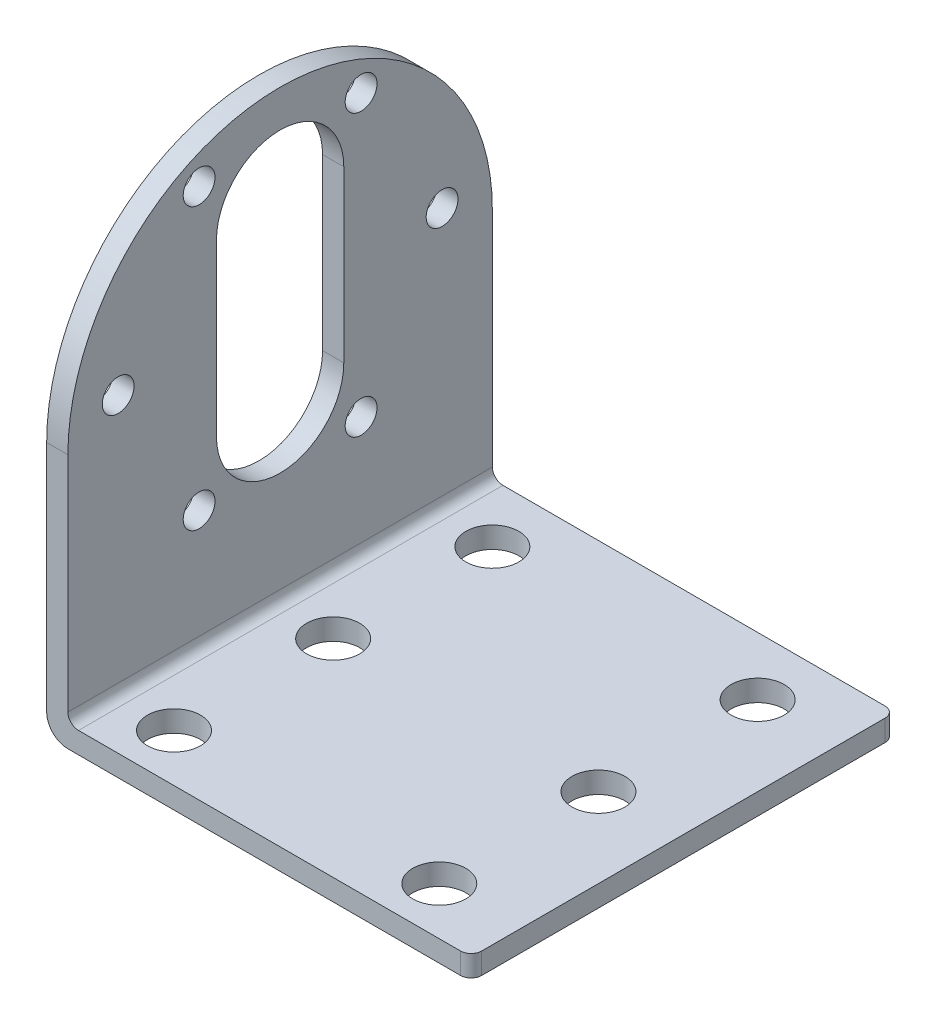
SolidWorks part; units mm, degrees
material "Ductile Iron"
ref_plane "Front Plane" through (0, 0, 0) normal (0, 0, 1) x (1, 0, 0)
ref_plane "Top Plane" through (0, 0, 0) normal (0, 1, 0) x (1, 0, 0)
ref_plane "Right Plane" through (0, 0, 0) normal (1, 0, 0) x (0, 0, -1)
sketch "Sketch2" plane through (0, 0, 0) normal (0, 0, 1) x (1, 0, 0)
  line L0 (2, 0) -> (40, 0)
  line L1 (0, 2) -> (0, 45)
  line L2 (2, 3) -> (2, 45)
  line L3 (3, 2) -> (40, 2)
  line L4 (40, 2) -> (40, 0)
  line L5 (0, 45) -> (2, 45)
  line L6 (2, 2) -> (40, 2) construction
  line L7 (2, 2) -> (2, 45) construction
  line L8 (0, 0) -> (40, 0) construction
  line L9 (0, 0) -> (0, 45) construction
  arc A0 (3, 2) -> (2, 3) centre (3, 3) cw
  arc A1 (2, 0) -> (0, 2) centre (2, 2) cw
  point P13 (0, 0)
  dimension "D4" = 1
  dimension "D5" = 2
  dimension "D1" = 40
  dimension "D3" = 45
  dimension "D2" = 2
extrude "Boss-Extrude1" add sketch "Sketch2" along normal blind 40
sketch "Sketch3" plane through (0, 2, 0) normal (0, 1, 0) x (1, 0, 0)
  line L0 (40, -40) -> (3, -40) construction
  point P0 (32.5, -35.5)
  point P6 (32.5, -5.5)
  point P9 (7.5, -5.5)
  point P11 (7.5, -35.5)
  dimension "D1" = 4.5
  dimension "D2" = 7.5
  dimension "D3" = 30
  dimension "D4" = 25
hole_wizard "Hole1" positions "Sketch3" profile "Sketch4" legacy end condition through all
sketch "Sketch4" plane through (32.5, 2, 35.5) normal (1, 0, 0) x (0, 0, 1)
  line L0 (0, 0) -> (0, 2)
  line L1 (0, 2) -> (2.5, 2)
  line L2 (2.5, 2) -> (2.5, 0)
  line L3 (2.5, 0) -> (0, 0)
  line L4 (0, 110) -> (0, -10) construction
  dimension "Diameter" = 5
  dimension "Depth" = 2
sketch "Sketch5" plane through (2, 0, 0) normal (1, 0, 0) x (0, 0, -1)
  line L0 (-40, 3) -> (-40, 45) construction
  line L1 (-40, 3) -> (-40, 45)
  line L2 (0, 3) -> (0, 45) construction
  line L3 (0, 3) -> (0, 45)
  line L4 (-40, 24) -> (-40, 3)
  line L5 (0, 3) -> (0, 24)
  arc A0 (-40, 24) -> (0, 24) centre (-20, 24) cw
  line M2 (0, 45) -> (-40, 45)
  line M3 (-40, 45) -> (-40, 3)
  dimension "D1" = 20
extrude "Cut-Extrude1" cut sketch "Sketch5" against normal blind 40 contours A0 L3 M3 M2 region at (2, 34.5, 39.5482)
sketch "Sketch6" plane through (2, 0, 0) normal (1, 0, 0) x (0, 0, -1)
  line L0 (-20, 34.5) -> (-20, 18.5) construction
  line L1 (-14, 34.5) -> (-14, 18.5)
  line L2 (-26, 34.5) -> (-26, 18.5)
  arc A0 (-14, 34.5) -> (-26, 34.5) centre (-20, 34.5) ccw
  arc A1 (-26, 18.5) -> (-14, 18.5) centre (-20, 18.5) ccw
  arc A2 (0, 24) -> (-40, 24) centre (-20, 24) ccw construction
  circle A3 centre (-20, 26.5) radius 15 construction
  point P3 (-20, 26.5)
  point P8 (-20, 40.5)
  point P9 (-20, 12.5)
  point P13 (-20, 44)
  dimension "D3" = 6
  dimension "D4" = 30
  dimension "D1" = 28
  dimension "D2" = 9.5
extrude "Cut-Extrude2" cut sketch "Sketch6" against normal blind 40
sketch "Sketch7" plane through (2, 0, 0) normal (1, 0, 0) x (0, 0, -1)
  line L0 (-20, 40.5) -> (-20, 12.5) construction
  line L1 (-35.265, 26.5) -> (-20, 26.5) construction
  line L2 (-20, 26.5) -> (-27.6325, 13.2801) construction
  arc A0 (-14, 34.5) -> (-26, 34.5) centre (-20, 34.5) ccw construction
  arc A1 (-26, 18.5) -> (-14, 18.5) centre (-20, 18.5) ccw construction
  circle A2 centre (-20, 26.5) radius 15.265 construction
  circle A3 centre (-4.735, 26.5) radius 1.5
  circle A4 centre (-35.265, 26.5) radius 1.5
  circle A5 centre (-27.6325, 13.2801) radius 1.5
  circle A6 centre (-12.3675, 13.2801) radius 1.5
  circle A7 centre (-27.6325, 39.7199) radius 1.5
  circle A8 centre (-12.3675, 39.7199) radius 1.5
  dimension "D1" = 30.53
  dimension "D2" = 3
  dimension "D3" = 3
  dimension "D4" = 3
  dimension "D6" = 3
  dimension "D7" = 3
  dimension "D8" = 3
  dimension "D5" = 60
extrude "Cut-Extrude3" cut sketch "Sketch7" against normal blind 40
fillet "Fillet1" radius 1 2 edges at (40, 1, 0) (40, 1, 40)
sketch "Sketch10" plane through (0, 2, 0) normal (0, 1, 0) x (1, 0, 0)
  line L0 (7.5, -3) -> (7.5, -38) construction
  line L1 (32.5, -3) -> (32.5, -38) construction
  circle A0 centre (7.5, -5.5) radius 2.5 construction
  circle A1 centre (7.5, -35.5) radius 2.5 construction
  circle A2 centre (32.5, -5.5) radius 2.5 construction
  circle A3 centre (32.5, -35.5) radius 2.5 construction
  circle A4 centre (7.5, -20.5) radius 2.5
  circle A5 centre (32.5, -20.5) radius 2.5
  dimension "D1" = 5
  dimension "D2" = 5
extrude "Cut-Extrude4" cut sketch "Sketch10" against normal blind 40
